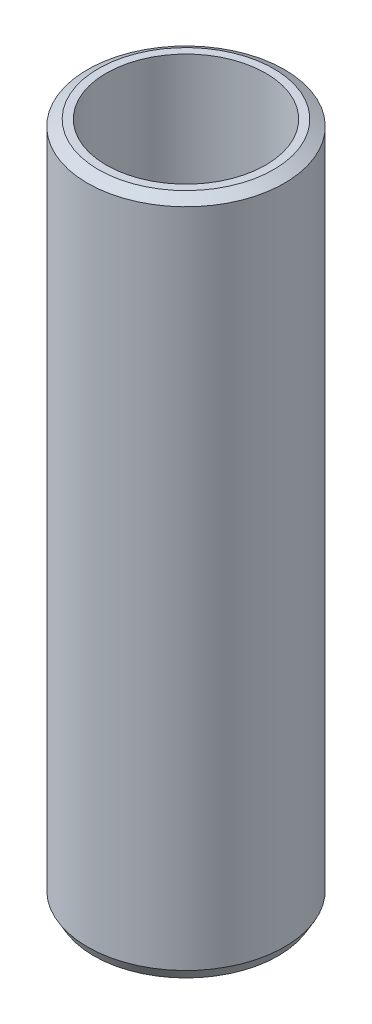
SolidWorks part; units mm, degrees
ref_plane "Front Plane" through (0, 0, 0) normal (0, 0, 1) x (1, 0, 0)
ref_plane "Top Plane" through (0, 0, 0) normal (0, 1, 0) x (1, 0, 0)
ref_plane "Right Plane" through (0, 0, 0) normal (1, 0, 0) x (0, 0, -1)
sketch "Sketch1" plane through (0, 0, 0) normal (0, 1, 0) x (1, 0, 0)
  circle A0 centre (0, 0) radius 57.5
  dimension "SHAFT_OD" = 115
extrude "Boss-Extrude1" add sketch "Sketch1" along normal blind 396.211
sketch "Sketch2" plane through (0, 0, 0) normal (0, 1, 0) x (1, 0, 0)
  circle A0 centre (0, 0) radius 46.5402
  dimension "BORE_D" = 93.0803
extrude "Cut-Extrude1" cut sketch "Sketch2" along normal through all
chamfer "Chamfer1" distance 3.6748 angle 60 2 edges at (0, 396.211, 57.5) (0, 0, 57.5) first distance on face at (0, 396.211, 57.5) first distance on face at (0, 0, 46.5402)
